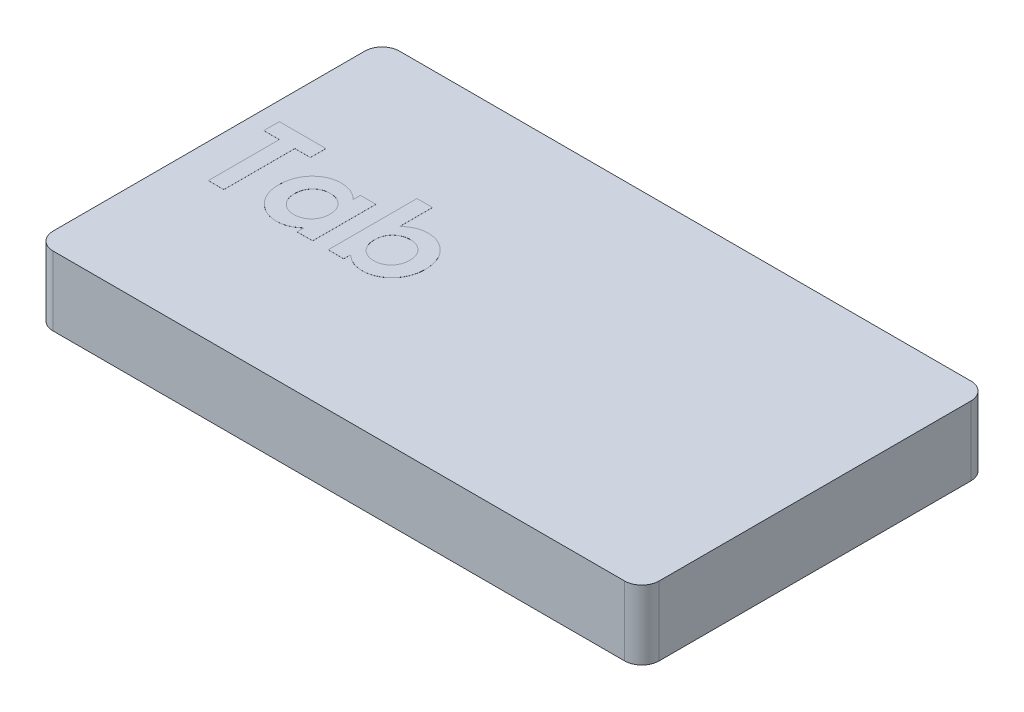
SolidWorks part; units mm, degrees
ref_plane "Front Plane" through (0, 0, 0) normal (0, 0, 1) x (1, 0, 0)
ref_plane "Top Plane" through (0, 0, 0) normal (0, 1, 0) x (1, 0, 0)
ref_plane "Right Plane" through (0, 0, 0) normal (1, 0, 0) x (0, 0, -1)
sketch "Sketch1" plane through (0, 0, 0) normal (0, 1, 0) x (1, 0, 0)
  line L0 (0, 0) -> (22.225, 0)
  line L1 (22.225, 0) -> (22.225, 12.7)
  line L2 (22.225, 12.7) -> (0, 12.7)
  line L3 (0, 12.7) -> (0, 0)
  dimension "D1" = 22.225
  dimension "D2" = 12.7
extrude "Boss-Extrude1" add sketch "Sketch1" along normal blind 2.54
fillet "Fillet1" radius 0.635 4 edges at (0, 1.27, -12.7) (22.225, 1.27, -12.7) (22.225, 1.27, 0) (0, 1.27, 0)
shell "Shell1" thickness 0.635 removed face at (11.1125, 0, -6.35)
sketch "Sketch2" plane through (0, 1.905, 0) normal (0, -1, 0) x (-1, 0, 0)
  line L0 (-0.635, 6.35) -> (-21.59, 6.35) construction
  line L1 (-0.635, 12.065) -> (-0.635, 0.635) construction
  line L2 (-21.59, 0.635) -> (-21.59, 12.065) construction
  line L3 (-11.1125, 0.635) -> (-11.1125, 12.065) construction
  line L4 (-0.635, 0.635) -> (-21.59, 0.635) construction
  line L5 (-21.59, 12.065) -> (-0.635, 12.065) construction
  circle A0 centre (-11.1125, 6.35) radius 2.54
  dimension "D1" = 5.08
extrude "Boss-Extrude2" add sketch "Sketch2" along normal up to surface (1.905 mm away) up to face at (11.1125, 0, -6.35)
sketch "Sketch3" plane through (0, 2.54, 0) normal (0, 1, 0) x (1, 0, 0)
  line L0 (0.635, 0) -> (21.59, 0) construction
  line L1 (0, 12.065) -> (0, 0.635) construction
  text T0 "<b>Tab</b>" font "Century Gothic" height 3.175
  dimension "D1" = 5.08
  dimension "D2" = 0.635
extrude "Boss-Extrude3" add sketch "Sketch3" along normal blind 0.0025
